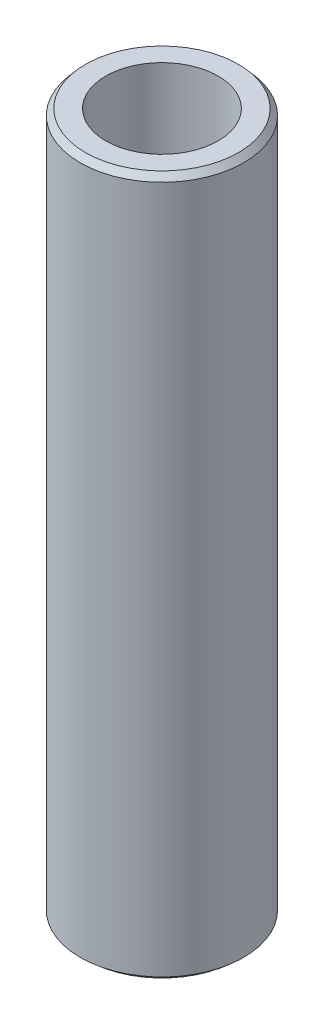
SolidWorks part; units mm, degrees
ref_plane "Front Plane" through (0, 0, 0) normal (0, 0, 1) x (1, 0, 0)
ref_plane "Top Plane" through (0, 0, 0) normal (0, 1, 0) x (1, 0, 0)
ref_plane "Right Plane" through (0, 0, 0) normal (1, 0, 0) x (0, 0, -1)
sketch "Sketch1" plane through (0, 0, 0) normal (0, 1, 0) x (1, 0, 0)
  circle A0 centre (0, 0) radius 60
  dimension "SHAFT_OD" = 120
extrude "Boss-Extrude1" add sketch "Sketch1" along normal blind 513.2898
sketch "Sketch2" plane through (0, 0, 0) normal (0, 1, 0) x (1, 0, 0)
  circle A0 centre (0, 0) radius 41.2255
  dimension "BORE_D" = 82.451
extrude "Cut-Extrude1" cut sketch "Sketch2" along normal through all
chamfer "Chamfer1" distance 4.509 angle 40.645 2 edges at (0, 513.2898, 60) (0, 0, 60) first distance on face at (0, 513.2898, 60) first distance on face at (0, 0, 41.2255)
